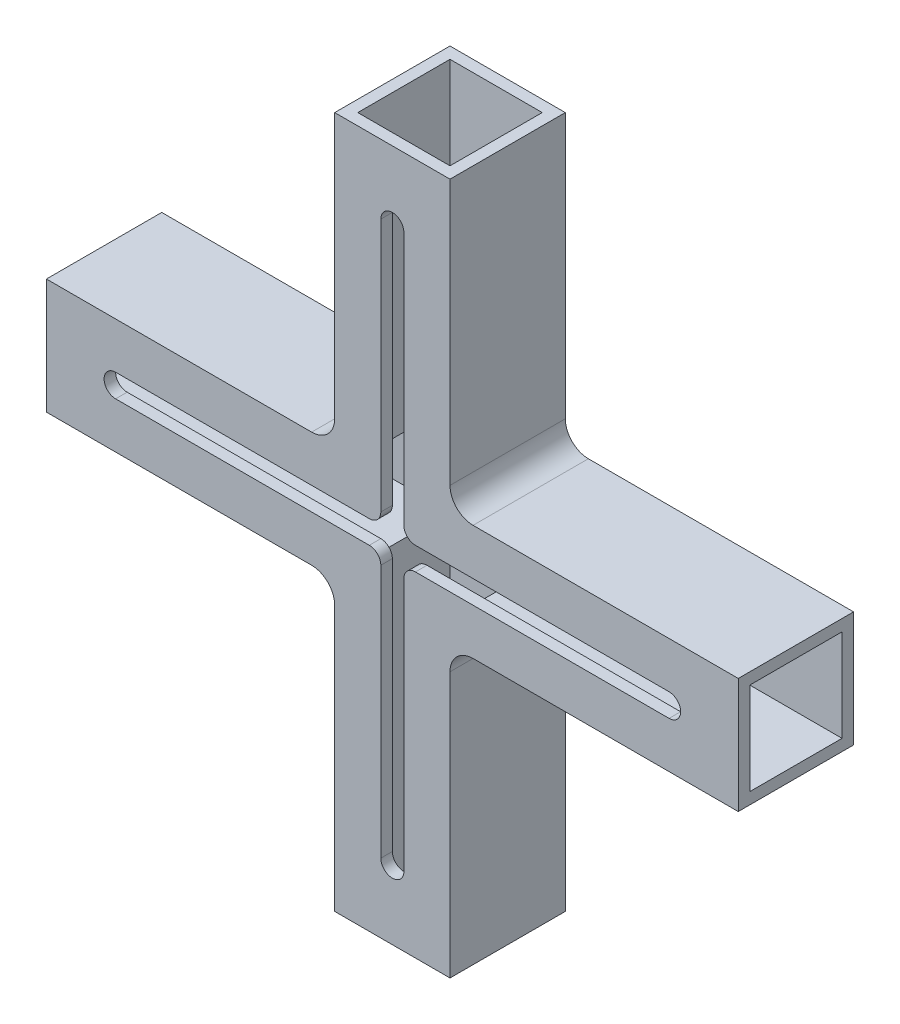
SolidWorks part; units mm, degrees
ref_plane "Front Plane" through (0, 0, 0) normal (0, 0, 1) x (1, 0, 0)
ref_plane "Top Plane" through (0, 0, 0) normal (0, 1, 0) x (1, 0, 0)
ref_plane "Right Plane" through (0, 0, 0) normal (1, 0, 0) x (0, 0, -1)
sketch "Sketch2" plane through (0, 0, 0) normal (0, 0, 1) x (1, 0, 0)
  line L2 (10, 60) -> (-10, 60)
  line L3 (-60, -10) -> (-14, -10)
  line L4 (-60, -10) -> (-60, 10)
  line L5 (-60, 10) -> (-14, 10)
  line L6 (60, -10) -> (60, 10)
  line L9 (10, 60) -> (10, 14)
  line L10 (10, -60) -> (-10, -60)
  line L11 (-10, 60) -> (-10, 14)
  line L15 (-10, -14) -> (-10, -60)
  line L19 (10, -14) -> (10, -60)
  line L20 (14, -10) -> (60, -10)
  line L21 (14, 10) -> (60, 10)
  arc A0 (-10, -14) -> (-14, -10) centre (-14, -14) ccw
  arc A1 (10, -14) -> (14, -10) centre (14, -14) cw
  arc A2 (14, 10) -> (10, 14) centre (14, 14) cw
  arc A3 (-10, 14) -> (-14, 10) centre (-14, 14) cw
  point P3 (0, 0)
  point P5 (0, 0)
  point P17 (10, -10)
  dimension "D1" = 4
extrude "Boss-Extrude1" add sketch "Sketch2" along normal mid plane 20
sketch "Sketch3" plane through (60, 0, 0) normal (1, 0, 0) x (0, 0, -1)
  line L1 (8, 8) -> (-8, 8)
  line L2 (8, 8) -> (8, -8)
  line L3 (8, -8) -> (-8, -8)
  line L4 (-8, 8) -> (-8, -8)
  line L5 (8, 8) -> (-8, -8) construction
  line L6 (8, -8) -> (-8, 8) construction
  point P0 (0, 0)
sketch "Sketch5" plane through (0, 60, 0) normal (0, 1, 0) x (1, 0, 0)
  line L1 (-8, -8) -> (8, -8)
  line L2 (-8, -8) -> (-8, 8)
  line L3 (-8, 8) -> (8, 8)
  line L4 (8, -8) -> (8, 8)
  line L5 (-8, -8) -> (8, 8) construction
  line L6 (-8, 8) -> (8, -8) construction
  point P0 (0, 0)
extrude "Cut-Extrude1" cut sketch "Sketch5" against normal up to surface (120 mm away) up to face at (0, -60, 0)
extrude "Cut-Extrude2" cut sketch "Sketch3" against normal up to surface (120 mm away) up to face at (-60, 0, 0)
sketch "Sketch6" plane through (0, 0, 10) normal (0, 0, 1) x (1, 0, 0)
  line L0 (-2, 4) -> (-2, 50)
  line L1 (2, -50) -> (-2, -50)
  line L2 (2, -50) -> (2, -4)
  line L3 (2, 50) -> (-2, 50)
  line L4 (-2, -50) -> (-2, -4)
  line L7 (50, -2) -> (4, -2)
  line L8 (50, -2) -> (50, 2)
  line L9 (50, 2) -> (4, 2)
  line L10 (-50, -2) -> (-50, 2)
  line L15 (2, 4) -> (2, 50)
  line L18 (-4, 2) -> (-50, 2)
  line L19 (-4, -2) -> (-50, -2)
  arc A0 (4, -2) -> (2, -4) centre (4, -4) ccw
  arc A1 (-2, -4) -> (-4, -2) centre (-4, -4) ccw
  arc A2 (4, 2) -> (2, 4) centre (4, 4) cw
  arc A3 (-2, 4) -> (-4, 2) centre (-4, 4) cw
  point P0 (0, 0)
  point P6 (0, 0)
  point P19 (-2, -2)
  point P24 (-2, 2)
  dimension "D1" = 2
extrude "Cut-Extrude3" cut sketch "Sketch6" against normal blind 2
fillet "Fillet1" 2 edges at (2, 50, 9) (-2, 50, 9) type full round first side face at (2, 27, 9) second side face at (-2, 27, 9) middle face at (0, 50, 9)
fillet "Fillet2" 2 edges at (2, -50, 9) (-2, -50, 9) type full round first side face at (2, -27, 9) second side face at (-2, -27, 9) middle face at (0, -50, 9)
fillet "Fillet3" 2 edges at (50, 2, 9) (50, -2, 9) type full round first side face at (27, 2, 9) second side face at (27, -2, 9) middle face at (50, 0, 9)
fillet "Fillet4" 2 edges at (-50, -2, 9) (-50, 2, 9) type full round first side face at (-27, -2, 9) second side face at (-27, 2, 9) middle face at (-50, 0, 9)
sketch "Sketch7" plane through (0, 0, -10) normal (0, 0, -1) x (-1, 0, 0)
  circle A0 centre (0, 0) radius 23
